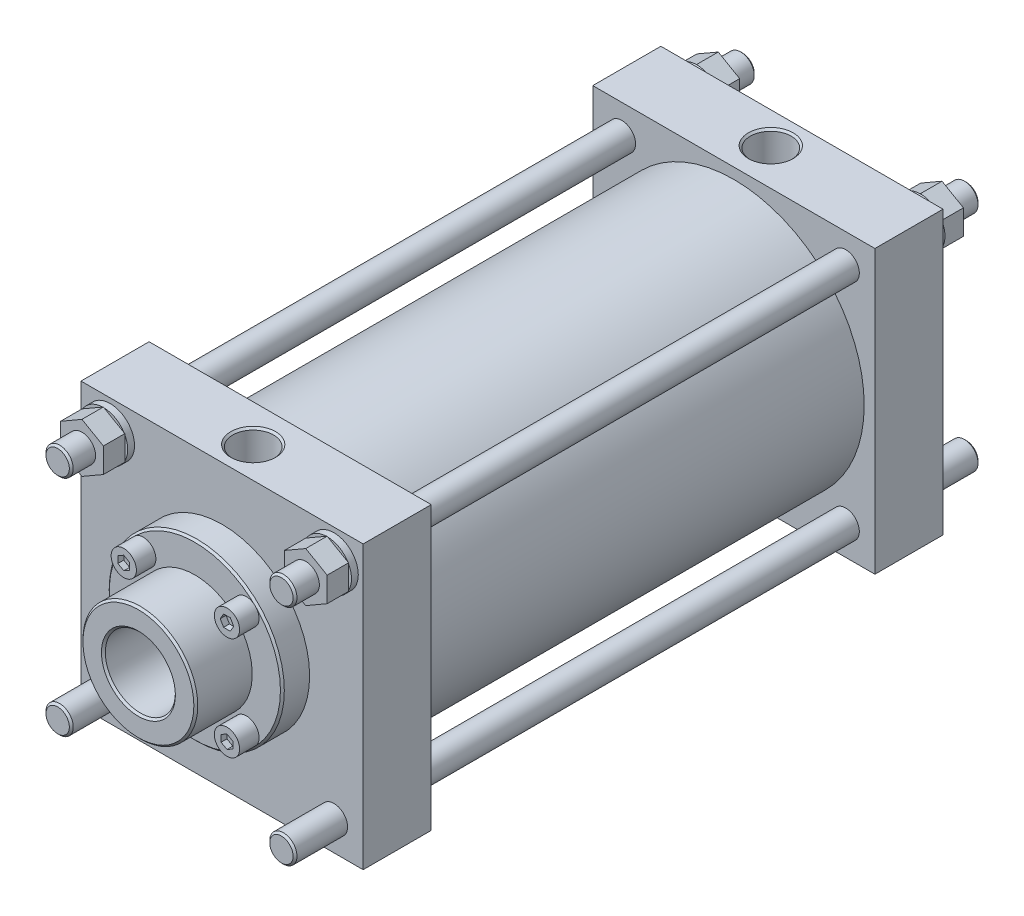
SolidWorks part; units mm, degrees
note: '?' marks a value the reader was unsure of.
ref_plane "Front" through (0, 0, 0) normal (0, 0, 1) x (1, 0, 0)
ref_plane "Top" through (0, 0, 0) normal (0, 1, 0) x (1, 0, 0)
ref_plane "Right" through (0, 0, 0) normal (1, 0, 0) x (0, 0, -1)
sketch "Sketch1" plane through (0, 0, 0) normal (0, 0, 1) x (1, 0, 0)
  circle A0 centre (0, 0) radius 67
  dimension "D1" = 134
extrude "Base-Extrude" add sketch "Sketch1" along normal up to surface (149 mm away) and the other way up to surface (149 mm away)
sketch "Sketch2" plane through (0, 0, 0) normal (1, 0, 0) x (0, 0, -1)
  line L0 (0, 0) -> (0, 180.6624) construction
  line L1 (-149, 72.5) -> (-114, 72.5)
  line L2 (-149, 72.5) -> (-149, -72.5)
  line L3 (-149, -72.5) -> (-114, -72.5)
  line L4 (-114, 72.5) -> (-114, -72.5)
  line L5 (-149, 67) -> (-149, -67) construction
  line L6 (114, 72.5) -> (114, -72.5)
  line L7 (149, -72.5) -> (114, -72.5)
  line L8 (149, 72.5) -> (149, -72.5)
  line L9 (149, 72.5) -> (114, 72.5)
  point P9 (-149, 0)
  dimension "N" = 35
  dimension "B" = 145
extrude "Covers" add sketch "Sketch2" against normal mid plane 145
sketch "Sketch3" plane through (0, 0, 0) normal (1, 0, 0) x (0, 0, -1)
  line L0 (0, 0) -> (-273.2647, 0) construction
  line L1 (-114, 0) -> (114, 0) construction
  line L2 (-149, 45) -> (-163, 45)
  line L3 (-149, 72.5) -> (-149, -72.5) construction
  line L4 (-163, 45) -> (-163, 29.5)
  line L5 (-163, 29.5) -> (-192, 29.5)
  line L6 (-192, 29.5) -> (-192, 0)
  line L7 (-192, 0) -> (-149, 0)
  line L8 (-149, 0) -> (-149, 45)
  dimension "EA" = 59
  dimension "E" = 90
  dimension "FA" = 14
  dimension "F" = 43
revolve "CoverNose" add sketch "Sketch3" angle 360 about L0
sketch "Sketch4" plane through (0, 0, 0) normal (0, 0, 1) x (1, 0, 0)
  line L0 (0, 0) -> (0, 99.2493) construction
  line L1 (0, 0) -> (94.6161, 0) construction
  line L2 (-57.5, 57.5) -> (-57.5, -57.5) construction
  line L3 (-57.5, -57.5) -> (57.5, -57.5) construction
  circle A0 centre (57.5, 57.5) radius 7
  circle A1 centre (-57.5, 57.5) radius 7
  circle A2 centre (-57.5, -57.5) radius 7
  circle A3 centre (57.5, -57.5) radius 7
  dimension "J" = 14
  dimension "C" = 115
extrude "TieRods" add sketch "Sketch4" along normal up to surface and the other way up to surface
sketch "Sketch5" plane through (0, 72.5, 0) normal (0, 1, 0) x (-1, 0, 0)
  line L0 (0, 114) -> (0, -114) construction
  line L1 (72.5, 149) -> (-72.5, 149) construction
  line L2 (0, 0) -> (-173.0019, 0) construction
  circle A0 centre (0, 133) radius 10.5
  circle A1 centre (0, -133) radius 10.5
  dimension "P" = 21
  dimension "G" = 16
extrude "Ports" cut sketch "Sketch5" against normal up to surface (72.5 mm away)
sketch "Sketch6" plane through (0, 0, 192) normal (0, 0, 1) x (1, 0, 0)
  circle A0 centre (0, 0) radius 18
  dimension "D" = 36
extrude "Bore" cut sketch "Sketch6" against normal up to surface (294.5 mm away)
sketch "Sketch7" plane through (0, 0, -102.5) normal (0, 0, 1) x (1, 0, 0)
  circle A0 centre (0, 0) radius 62.5
  dimension "Bore" = 125
extrude "StrokeChamber" cut sketch "Sketch7" along normal up to surface (205 mm away)
chamfer "Chamfer1" distance 1 angle 45 13 edges at (-45, 0, 163) (-29.5, 0, 192) (50.5, 57.5, -176) (64.5, 57.5, 176) (-64.5, 57.5, -176) (-50.5, 57.5, 176) (-64.5, -57.5, -176) (-50.5, -57.5, 176) (50.5, -57.5, -176) (64.5, -57.5, 176) (0, 72.5, 143.5) (0, 72.5, -143.5) (18, 0, 192)
sketch "Sketch12" plane through (0, 0, 149) normal (0, 0, 1) x (1, 0, 0)
  circle A0 centre (-57.5, 57.5) radius 12.5
  circle A1 centre (57.5, 57.5) radius 12.5
  circle A2 centre (57.5, 57.5) radius 7 construction
  circle A3 centre (-57.5, 57.5) radius 7 construction
  circle A4 centre (57.5, 57.5) radius 7
  circle A5 centre (-57.5, 57.5) radius 7
  dimension "D1" = 25
extrude "FrontTopWashers" add sketch "Sketch12" along normal blind 3.5 separate body
sketch "Sketch8" plane through (0, 0, 152.5) normal (0, 0, 1) x (1, 0, 0)
  line L1 (68.5, 63.8509) -> (57.5, 70.2017)
  line L2 (-57.5, 70.2017) -> (-68.5, 63.8509)
  line L3 (-68.5, 63.8509) -> (-68.5, 51.1491)
  line L4 (-68.5, 51.1491) -> (-57.5, 44.7983)
  line L5 (-57.5, 44.7983) -> (-46.5, 51.1491)
  line L6 (-46.5, 51.1491) -> (-46.5, 63.8509)
  line L7 (-46.5, 63.8509) -> (-57.5, 70.2017)
  line L8 (57.5, 70.2017) -> (46.5, 63.8509)
  line L9 (46.5, 63.8509) -> (46.5, 51.1491)
  line L10 (46.5, 51.1491) -> (57.5, 44.7983)
  line L11 (57.5, 44.7983) -> (68.5, 51.1491)
  line L12 (68.5, 51.1491) -> (68.5, 63.8509)
  circle A0 centre (-57.5, 57.5) radius 11 construction
  circle A1 centre (57.5, 57.5) radius 11 construction
  dimension "D1" = 22
extrude "FrontTopNuts" add sketch "Sketch8" along normal blind 11
sketch "Sketch13" plane through (0, 0, 149) normal (0, 0, 1) x (1, 0, 0)
  circle A0 centre (-57.5, -57.5) radius 12.5
  circle A1 centre (57.5, -57.5) radius 12.5
  circle A2 centre (57.5, -57.5) radius 7 construction
  circle A3 centre (-57.5, -57.5) radius 7 construction
  circle A4 centre (57.5, -57.5) radius 7
  circle A5 centre (-57.5, -57.5) radius 7
  dimension "D1" = 25
extrude "FrontBottomWashers" [suppressed] add sketch "Sketch13" along normal blind 3.5 separate body
sketch "Sketch9" [suppressed] plane through (0, 0, 102.5) normal (0, 0, 1) x (1, 0, 0)
  line L1 (-46.5, -63.8509) -> (-46.5, -51.1491)
  line L2 (-46.5, -51.1491) -> (-57.5, -44.7983)
  line L3 (-57.5, -44.7983) -> (-68.5, -51.1491)
  line L4 (-68.5, -51.1491) -> (-68.5, -63.8509)
  line L5 (-68.5, -63.8509) -> (-57.5, -70.2017)
  line L6 (-57.5, -70.2017) -> (-46.5, -63.8509)
  line L7 (68.5, -51.1491) -> (57.5, -44.7983)
  line L8 (57.5, -44.7983) -> (46.5, -51.1491)
  line L9 (46.5, -51.1491) -> (46.5, -63.8509)
  line L10 (46.5, -63.8509) -> (57.5, -70.2017)
  line L11 (57.5, -70.2017) -> (68.5, -63.8509)
  line L12 (68.5, -63.8509) -> (68.5, -51.1491)
  circle A0 centre (-57.5, -57.5) radius 11 construction
  circle A1 centre (57.5, -57.5) radius 11 construction
  dimension "D1" = 22
extrude "FrontBottomNuts" [suppressed] add sketch "Sketch9" along normal blind 11
sketch "Sketch14" plane through (0, 0, -149) normal (0, 0, -1) x (-1, 0, 0)
  circle A0 centre (-57.5, 57.5) radius 12.5
  circle A1 centre (57.5, 57.5) radius 12.5
  circle A2 centre (57.5, 57.5) radius 7 construction
  circle A3 centre (-57.5, 57.5) radius 7 construction
  circle A4 centre (57.5, 57.5) radius 7
  circle A5 centre (-57.5, 57.5) radius 7
  dimension "D1" = 25
extrude "RearTopWashers" add sketch "Sketch14" along normal blind 3.5 separate body
sketch "Sketch10" plane through (0, 0, -152.5) normal (0, 0, -1) x (-1, 0, 0)
  line L1 (-46.5, 63.8509) -> (-57.5, 70.2017)
  line L2 (-57.5, 70.2017) -> (-68.5, 63.8509)
  line L3 (-68.5, 63.8509) -> (-68.5, 51.1491)
  line L4 (-68.5, 51.1491) -> (-57.5, 44.7983)
  line L5 (-57.5, 44.7983) -> (-46.5, 51.1491)
  line L6 (-46.5, 51.1491) -> (-46.5, 63.8509)
  line L7 (68.5, 63.8509) -> (57.5, 70.2017)
  line L8 (57.5, 70.2017) -> (46.5, 63.8509)
  line L9 (46.5, 63.8509) -> (46.5, 51.1491)
  line L10 (46.5, 51.1491) -> (57.5, 44.7983)
  line L11 (57.5, 44.7983) -> (68.5, 51.1491)
  line L12 (68.5, 51.1491) -> (68.5, 63.8509)
  circle A0 centre (-57.5, 57.5) radius 11 construction
  circle A1 centre (57.5, 57.5) radius 11 construction
  circle A6 centre (-57.5, 57.5) radius 7 construction
  circle A7 centre (57.5, 57.5) radius 7 construction
  dimension "D1" = 22
extrude "RearTopNuts" add sketch "Sketch10" along normal blind 11
sketch "Sketch15" plane through (0, 0, -149) normal (0, 0, -1) x (-1, 0, 0)
  circle A0 centre (-57.5, -57.5) radius 12.5
  circle A1 centre (57.5, -57.5) radius 12.5
  circle A2 centre (57.5, -57.5) radius 7 construction
  circle A3 centre (-57.5, -57.5) radius 7 construction
  circle A4 centre (57.5, -57.5) radius 7
  circle A5 centre (-57.5, -57.5) radius 7
  dimension "D1" = 25
extrude "RearBottomWashers" [suppressed] add sketch "Sketch15" along normal blind 3.5 separate body
sketch "Sketch11" [suppressed] plane through (0, 0, -102.5) normal (0, 0, -1) x (-1, 0, 0)
  line L1 (-68.5, -51.1491) -> (-68.5, -63.8509)
  line L2 (-68.5, -63.8509) -> (-57.5, -70.2017)
  line L3 (-57.5, -70.2017) -> (-46.5, -63.8509)
  line L4 (-46.5, -63.8509) -> (-46.5, -51.1491)
  line L5 (-46.5, -51.1491) -> (-57.5, -44.7983)
  line L6 (-57.5, -44.7983) -> (-68.5, -51.1491)
  line L7 (46.5, -51.1491) -> (46.5, -63.8509)
  line L8 (46.5, -63.8509) -> (57.5, -70.2017)
  line L9 (57.5, -70.2017) -> (68.5, -63.8509)
  line L10 (68.5, -63.8509) -> (68.5, -51.1491)
  line L11 (68.5, -51.1491) -> (57.5, -44.7983)
  line L12 (57.5, -44.7983) -> (46.5, -51.1491)
  circle A0 centre (-57.5, -57.5) radius 11 construction
  circle A1 centre (57.5, -57.5) radius 11 construction
  circle A2 centre (-57.5, -57.5) radius 12.5 construction
  circle A5 centre (57.5, -57.5) radius 12.5 construction
  dimension "D1" = 22
extrude "RearBottomNuts" [suppressed] add sketch "Sketch11" along normal blind 11
sketch "Sketch16" plane through (0, 0, 163) normal (0, 0, 1) x (1, 0, 0)
  line L0 (0, 0) -> (0, 63.2818) construction
  line L1 (0, 0) -> (-26.5165, 26.5165) construction
  circle A0 centre (0, 0) radius 37.5 construction
  circle A2 centre (-26.5165, 26.5165) radius 6.5
  dimension "D1" = 75
  dimension "D2" = 13
  dimension "D3" = 45
extrude "Extrude5" add sketch "Sketch16" along normal blind 10 separate body
sketch "Sketch17" plane through (0, 0, 173) normal (0, 0, 1) x (1, 0, 0)
  line L1 (-26.5165, 29.9806) -> (-29.5165, 28.2486)
  line L2 (-29.5165, 28.2486) -> (-29.5165, 24.7845)
  line L3 (-29.5165, 24.7845) -> (-26.5165, 23.0524)
  line L4 (-26.5165, 23.0524) -> (-23.5165, 24.7845)
  line L5 (-23.5165, 24.7845) -> (-23.5165, 28.2486)
  line L6 (-23.5165, 28.2486) -> (-26.5165, 29.9806)
  circle A0 centre (-26.5165, 26.5165) radius 3 construction
  dimension "D1" = 6
extrude "Cut-Extrude1" cut sketch "Sketch17" against normal blind 3
ref_axis "Axis1" through (0, 0, -80.9) along (0, 0, 1)?
pattern_circular "CirPattern1" count 4 over 360 about axis through (0, 0, 0) along (0, 0, 1) of bodies 121
